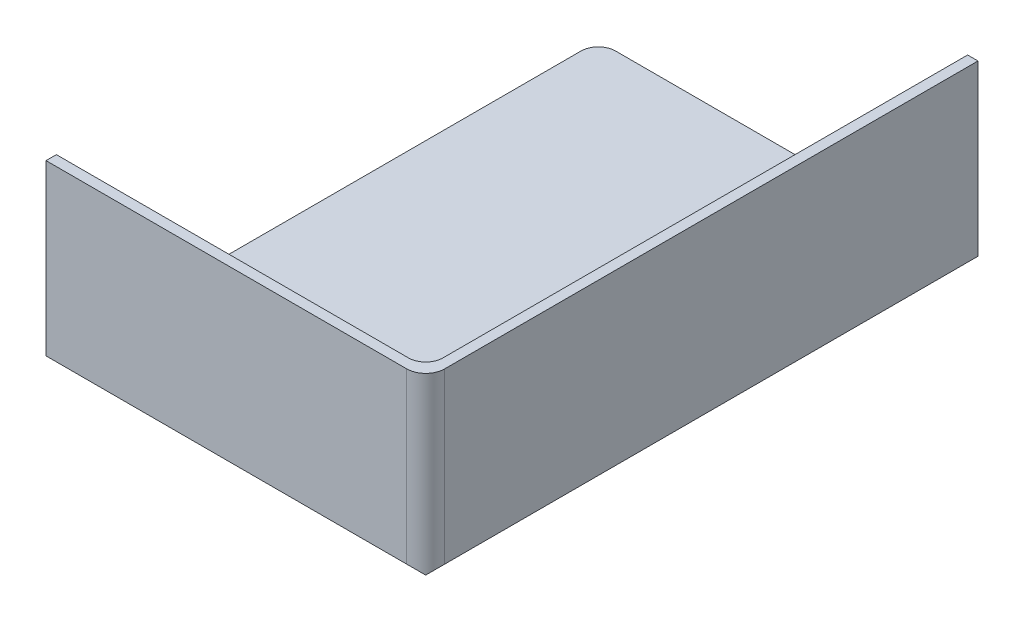
SolidWorks part; units mm, degrees
ref_plane "前视基准面" through (0, 0, 0) normal (0, 0, 1) x (1, 0, 0)
ref_plane "上视基准面" through (0, 0, 0) normal (0, 1, 0) x (1, 0, 0)
ref_plane "右视基准面" through (0, 0, 0) normal (1, 0, 0) x (0, 0, -1)
other "Configuration Table"
sketch "草图1" plane through (0, 0, 0) normal (0, 1, 0) x (1, 0, 0)
  line L1 (0, 0) -> (110, 0)
  line L2 (0, 0) -> (0, 160)
  line L3 (0, 160) -> (110, 160)
  line L4 (110, 0) -> (110, 160)
  dimension "D1" = 160
  dimension "D2" = 110
extrude "凸台-拉伸1" add sketch "草图1" along normal blind 3
sketch "草图2" plane through (0, 3, 0) normal (0, 1, 0) x (1, 0, 0)
  line L0 (110, 0) -> (110, 160) construction
  line L1 (0, 0) -> (110, 0)
  line L2 (0, 0) -> (0, 3)
  line L3 (0, 3) -> (107, 3)
  line L4 (110, 0) -> (110, 3)
  line L5 (110, 160) -> (0, 160) construction
  line L7 (110, 3) -> (110, 160)
  line L8 (110, 160) -> (107, 160)
  line L9 (107, 3) -> (107, 160)
  dimension "D1" = 3
  dimension "D2" = 3
extrude "凸台-拉伸2" add sketch "草图2" along normal blind 50
fillet "圆角1" radius 5 2 edges at (53.5, 3, -3) (107, 3, -81.5)
chamfer "倒角1" distance 4 angle 45 2 edges at (55, 0, 0) (110, 0, -80)
fillet "圆角2" radius 5 1 edges at (0, 1.5, -160)
fillet "圆角3" radius 5 2 edges at (105.5355, 4.4645, -4.4645) (107, 30.5, -3)
fillet "圆角4" radius 5.5 1 edges at (110, 28.5, 0)
